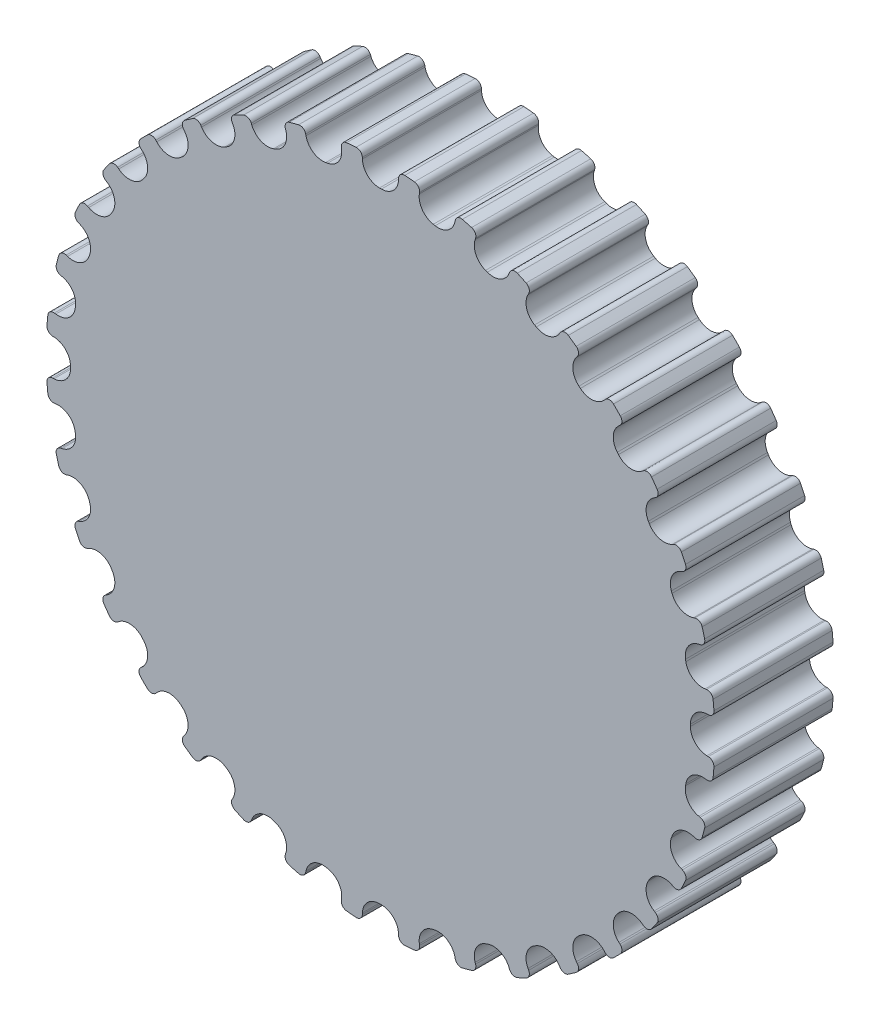
SolidWorks part; units mm, degrees
material "ABS"
ref_plane "前视基准面" through (0, 0, 0) normal (0, 0, 1) x (1, 0, 0)
ref_plane "上视基准面" through (0, 0, 0) normal (0, 1, 0) x (1, 0, 0)
ref_plane "右视基准面" through (0, 0, 0) normal (1, 0, 0) x (0, 0, -1)
sketch "草图1" plane through (0, 0, 0) normal (0, 0, 1) x (1, 0, 0)
  line L0 (0, 0) -> (0, 28.0759) construction
  line L1 (-2.5, 27.9644) -> (2.5, 27.9644) construction
  line L2 (-0.081, 26.0239) -> (0.081, 26.0239)
  line L3 (1.5181, 27.4117) -> (1.5223, 27.5316)
  line L4 (-1.5181, 27.4117) -> (-1.5223, 27.5316)
  line L5 (3.2649, 27.2589) -> (3.2816, 27.3777)
  line L6 (4.4392, 25.6426) -> (4.5988, 25.6145)
  line L7 (6.2551, 26.7316) -> (6.28, 26.849)
  line L8 (7.9488, 26.2778) -> (7.9859, 26.3919)
  line L9 (8.8246, 24.4822) -> (8.9768, 24.4268)
  line L10 (10.8019, 25.2393) -> (10.8469, 25.3506)
  line L11 (12.3911, 24.4983) -> (12.4474, 24.6042)
  line L12 (12.9418, 22.5778) -> (13.0821, 22.4968)
  line L13 (15.0206, 22.9802) -> (15.0842, 23.0819)
  line L14 (16.457, 21.9744) -> (16.5308, 22.069)
  line L15 (16.6658, 19.9875) -> (16.7899, 19.8834)
  line L16 (18.7829, 20.0228) -> (18.8631, 20.1119)
  line L17 (20.0228, 18.7829) -> (20.1119, 18.8631)
  line L18 (19.8834, 16.7899) -> (19.9875, 16.6658)
  line L19 (21.9744, 16.457) -> (22.069, 16.5308)
  line L20 (22.9802, 15.0206) -> (23.0819, 15.0842)
  line L21 (22.4968, 13.0821) -> (22.5778, 12.9418)
  line L22 (24.4983, 12.3911) -> (24.6042, 12.4474)
  line L23 (25.2393, 10.8019) -> (25.3506, 10.8469)
  line L24 (24.4268, 8.9768) -> (24.4822, 8.8246)
  line L25 (26.2778, 7.9488) -> (26.3919, 7.9859)
  line L26 (26.7316, 6.2551) -> (26.849, 6.28)
  line L27 (25.6145, 4.5988) -> (25.6426, 4.4392)
  line L28 (27.2589, 3.2649) -> (27.3777, 3.2816)
  line L29 (27.4117, 1.5181) -> (27.5316, 1.5223)
  line L30 (26.0239, 0.081) -> (26.0239, -0.081)
  line L31 (27.4117, -1.5181) -> (27.5316, -1.5223)
  line L32 (27.2589, -3.2649) -> (27.3777, -3.2816)
  line L33 (25.6426, -4.4392) -> (25.6145, -4.5988)
  line L34 (26.7316, -6.2551) -> (26.849, -6.28)
  line L35 (26.2778, -7.9488) -> (26.3919, -7.9859)
  line L36 (24.4822, -8.8246) -> (24.4268, -8.9768)
  line L37 (25.2393, -10.8019) -> (25.3506, -10.8469)
  line L38 (24.4983, -12.3911) -> (24.6042, -12.4474)
  line L39 (22.5778, -12.9418) -> (22.4968, -13.0821)
  line L40 (22.9802, -15.0206) -> (23.0819, -15.0842)
  line L41 (21.9744, -16.457) -> (22.069, -16.5308)
  line L42 (19.9875, -16.6658) -> (19.8834, -16.7899)
  line L43 (20.0228, -18.7829) -> (20.1119, -18.8631)
  line L44 (18.7829, -20.0228) -> (18.8631, -20.1119)
  line L45 (16.7899, -19.8834) -> (16.6658, -19.9875)
  line L46 (16.457, -21.9744) -> (16.5308, -22.069)
  line L47 (15.0206, -22.9802) -> (15.0842, -23.0819)
  line L48 (13.0821, -22.4968) -> (12.9418, -22.5778)
  line L49 (12.3911, -24.4983) -> (12.4474, -24.6042)
  line L50 (10.8019, -25.2393) -> (10.8469, -25.3506)
  line L51 (8.9768, -24.4268) -> (8.8246, -24.4822)
  line L52 (7.9488, -26.2778) -> (7.9859, -26.3919)
  line L53 (6.2551, -26.7316) -> (6.28, -26.849)
  line L54 (4.5988, -25.6145) -> (4.4392, -25.6426)
  line L55 (3.2649, -27.2589) -> (3.2816, -27.3777)
  line L56 (1.5181, -27.4117) -> (1.5223, -27.5316)
  line L57 (0.081, -26.0239) -> (-0.081, -26.0239)
  line L58 (-1.5181, -27.4117) -> (-1.5223, -27.5316)
  line L59 (-3.2649, -27.2589) -> (-3.2816, -27.3777)
  line L60 (-4.4392, -25.6426) -> (-4.5988, -25.6145)
  line L61 (-6.2551, -26.7316) -> (-6.28, -26.849)
  line L62 (-7.9488, -26.2778) -> (-7.9859, -26.3919)
  line L63 (-8.8246, -24.4822) -> (-8.9768, -24.4268)
  line L64 (-10.8019, -25.2393) -> (-10.8469, -25.3506)
  line L65 (-12.3911, -24.4983) -> (-12.4474, -24.6042)
  line L66 (-12.9418, -22.5778) -> (-13.0821, -22.4968)
  line L67 (-15.0206, -22.9802) -> (-15.0842, -23.0819)
  line L68 (-16.457, -21.9744) -> (-16.5308, -22.069)
  line L69 (-16.6658, -19.9875) -> (-16.7899, -19.8834)
  line L70 (-18.7829, -20.0228) -> (-18.8631, -20.1119)
  line L71 (-20.0228, -18.7829) -> (-20.1119, -18.8631)
  line L72 (-19.8834, -16.7899) -> (-19.9875, -16.6658)
  line L73 (-21.9744, -16.457) -> (-22.069, -16.5308)
  line L74 (-22.9802, -15.0206) -> (-23.0819, -15.0842)
  line L75 (-22.4968, -13.0821) -> (-22.5778, -12.9418)
  line L76 (-24.4983, -12.3911) -> (-24.6042, -12.4474)
  line L77 (-25.2393, -10.8019) -> (-25.3506, -10.8469)
  line L78 (-24.4268, -8.9768) -> (-24.4822, -8.8246)
  line L79 (-26.2778, -7.9488) -> (-26.3919, -7.9859)
  line L80 (-26.7316, -6.2551) -> (-26.849, -6.28)
  line L81 (-25.6145, -4.5988) -> (-25.6426, -4.4392)
  line L82 (-27.2589, -3.2649) -> (-27.3777, -3.2816)
  line L83 (-27.4117, -1.5181) -> (-27.5316, -1.5223)
  line L84 (-26.0239, -0.081) -> (-26.0239, 0.081)
  line L85 (-27.4117, 1.5181) -> (-27.5316, 1.5223)
  line L86 (-27.2589, 3.2649) -> (-27.3777, 3.2816)
  line L87 (-25.6426, 4.4392) -> (-25.6145, 4.5988)
  line L88 (-26.7316, 6.2551) -> (-26.849, 6.28)
  line L89 (-26.2778, 7.9488) -> (-26.3919, 7.9859)
  line L90 (-24.4822, 8.8246) -> (-24.4268, 8.9768)
  line L91 (-25.2393, 10.8019) -> (-25.3506, 10.8469)
  line L92 (-24.4983, 12.3911) -> (-24.6042, 12.4474)
  line L93 (-22.5778, 12.9418) -> (-22.4968, 13.0821)
  line L94 (-22.9802, 15.0206) -> (-23.0819, 15.0842)
  line L95 (-21.9744, 16.457) -> (-22.069, 16.5308)
  line L96 (-19.9875, 16.6658) -> (-19.8834, 16.7899)
  line L97 (-20.0228, 18.7829) -> (-20.1119, 18.8631)
  line L98 (-18.7829, 20.0228) -> (-18.8631, 20.1119)
  line L99 (-16.7899, 19.8834) -> (-16.6658, 19.9875)
  line L100 (-16.457, 21.9744) -> (-16.5308, 22.069)
  line L101 (-15.0206, 22.9802) -> (-15.0842, 23.0819)
  line L102 (-13.0821, 22.4968) -> (-12.9418, 22.5778)
  line L103 (-12.3911, 24.4983) -> (-12.4474, 24.6042)
  line L104 (-10.8019, 25.2393) -> (-10.8469, 25.3506)
  line L105 (-8.9768, 24.4268) -> (-8.8246, 24.4822)
  line L106 (-7.9488, 26.2778) -> (-7.9859, 26.3919)
  line L107 (-6.2551, 26.7316) -> (-6.28, 26.849)
  line L108 (-4.5988, 25.6145) -> (-4.4392, 25.6426)
  line L109 (-3.2649, 27.2589) -> (-3.2816, 27.3777)
  circle A0 centre (0, 0) radius 28.0759 construction
  arc A1 (0.081, 26.0239) -> (1.5181, 27.4117) centre (0.081, 27.4619) ccw
  arc A2 (1.5223, 27.5316) -> (2.0456, 28.0013) centre (2.01, 27.5146) cw
  arc A3 (2.0456, 28.0013) -> (2.5, 27.9644) centre (0, 0) cw
  arc A4 (-2.0456, 28.0013) -> (-2.5, 27.9644) centre (0, 0) ccw
  arc A5 (-1.5223, 27.5316) -> (-2.0456, 28.0013) centre (-2.01, 27.5146) ccw
  arc A6 (-0.081, 26.0239) -> (-1.5181, 27.4117) centre (-0.081, 27.4619) cw
  arc A7 (2.8479, 27.9311) -> (2.3939, 27.9736) centre (0, 0) ccw
  arc A8 (3.2816, 27.3777) -> (2.8479, 27.9311) centre (2.7984, 27.4456) ccw
  arc A9 (4.4392, 25.6426) -> (3.2649, 27.2589) centre (4.6889, 27.0587) cw
  arc A10 (4.5988, 25.6145) -> (6.2551, 26.7316) centre (4.8485, 27.0306) ccw
  arc A11 (6.28, 26.849) -> (6.8769, 27.2207) centre (6.7573, 26.7475) cw
  arc A12 (6.8769, 27.2207) -> (7.318, 27.1054) centre (0, 0) cw
  arc A13 (7.6548, 27.0122) -> (7.2151, 27.133) centre (0, 0) ccw
  arc A14 (7.9859, 26.3919) -> (7.6548, 27.0122) centre (7.5217, 26.5427) ccw
  arc A15 (8.8246, 24.4822) -> (7.9488, 26.2778) centre (9.3164, 25.8334) cw
  arc A16 (8.9768, 24.4268) -> (10.8019, 25.2393) centre (9.4686, 25.778) ccw
  arc A17 (10.8469, 25.3506) -> (11.4992, 25.613) centre (11.2993, 25.1678) cw
  arc A18 (11.4992, 25.613) -> (11.9136, 25.4229) centre (0, 0) cw
  arc A19 (12.2291, 25.2726) -> (11.8171, 25.4678) centre (0, 0) ccw
  arc A20 (12.4474, 24.6042) -> (12.2291, 25.2726) centre (12.0166, 24.8333) ccw
  arc A21 (12.9418, 22.5778) -> (12.3911, 24.4983) centre (13.6608, 23.8232) cw
  arc A22 (13.0821, 22.4968) -> (15.0206, 22.9802) centre (13.8011, 23.7422) ccw
  arc A23 (15.0842, 23.0819) -> (15.7722, 23.227) centre (15.498, 22.8233) cw
  arc A24 (15.7722, 23.227) -> (16.1472, 22.9678) centre (0, 0) cw
  arc A25 (16.4319, 22.7651) -> (16.06, 23.0289) centre (0, 0) ccw
  arc A26 (16.5308, 22.069) -> (16.4319, 22.7651) centre (16.1463, 22.3694) ccw
  arc A27 (16.6658, 19.9875) -> (16.457, 21.9744) centre (17.5901, 21.0891) cw
  arc A28 (16.7899, 19.8834) -> (18.7829, 20.0228) centre (17.7142, 20.985) ccw
  arc A29 (18.8631, 20.1119) -> (19.5659, 20.1354) centre (19.2258, 19.7854) cw
  arc A30 (19.5659, 20.1354) -> (19.8903, 19.815) centre (0, 0) cw
  arc A31 (20.1354, 19.5659) -> (19.815, 19.8903) centre (0, 0) ccw
  arc A32 (20.1119, 18.8631) -> (20.1354, 19.5659) centre (19.7854, 19.2258) ccw
  arc A33 (19.8834, 16.7899) -> (20.0228, 18.7829) centre (20.985, 17.7142) cw
  arc A34 (19.9875, 16.6658) -> (21.9744, 16.457) centre (21.0891, 17.5901) ccw
  arc A35 (22.069, 16.5308) -> (22.7651, 16.4319) centre (22.3694, 16.1463) cw
  arc A36 (22.7651, 16.4319) -> (23.0289, 16.06) centre (0, 0) cw
  arc A37 (23.227, 15.7722) -> (22.9678, 16.1472) centre (0, 0) ccw
  arc A38 (23.0819, 15.0842) -> (23.227, 15.7722) centre (22.8233, 15.498) ccw
  arc A39 (22.4968, 13.0821) -> (22.9802, 15.0206) centre (23.7422, 13.8011) cw
  arc A40 (22.5778, 12.9418) -> (24.4983, 12.3911) centre (23.8232, 13.6608) ccw
  arc A41 (24.6042, 12.4474) -> (25.2726, 12.2291) centre (24.8333, 12.0166) cw
  arc A42 (25.2726, 12.2291) -> (25.4678, 11.8171) centre (0, 0) cw
  arc A43 (25.613, 11.4992) -> (25.4229, 11.9136) centre (0, 0) ccw
  arc A44 (25.3506, 10.8469) -> (25.613, 11.4992) centre (25.1678, 11.2993) ccw
  arc A45 (24.4268, 8.9768) -> (25.2393, 10.8019) centre (25.778, 9.4686) cw
  arc A46 (24.4822, 8.8246) -> (26.2778, 7.9488) centre (25.8334, 9.3164) ccw
  arc A47 (26.3919, 7.9859) -> (27.0122, 7.6548) centre (26.5427, 7.5217) cw
  arc A48 (27.0122, 7.6548) -> (27.133, 7.2151) centre (0, 0) cw
  arc A49 (27.2207, 6.8769) -> (27.1054, 7.318) centre (0, 0) ccw
  arc A50 (26.849, 6.28) -> (27.2207, 6.8769) centre (26.7475, 6.7573) ccw
  arc A51 (25.6145, 4.5988) -> (26.7316, 6.2551) centre (27.0306, 4.8485) cw
  arc A52 (25.6426, 4.4392) -> (27.2589, 3.2649) centre (27.0587, 4.6889) ccw
  arc A53 (27.3777, 3.2816) -> (27.9311, 2.8479) centre (27.4456, 2.7984) cw
  arc A54 (27.9311, 2.8479) -> (27.9736, 2.3939) centre (0, 0) cw
  arc A55 (28.0013, 2.0456) -> (27.9644, 2.5) centre (0, 0) ccw
  arc A56 (27.5316, 1.5223) -> (28.0013, 2.0456) centre (27.5146, 2.01) ccw
  arc A57 (26.0239, 0.081) -> (27.4117, 1.5181) centre (27.4619, 0.081) cw
  arc A58 (26.0239, -0.081) -> (27.4117, -1.5181) centre (27.4619, -0.081) ccw
  arc A59 (27.5316, -1.5223) -> (28.0013, -2.0456) centre (27.5146, -2.01) cw
  arc A60 (28.0013, -2.0456) -> (27.9644, -2.5) centre (0, 0) cw
  arc A61 (27.9311, -2.8479) -> (27.9736, -2.3939) centre (0, 0) ccw
  arc A62 (27.3777, -3.2816) -> (27.9311, -2.8479) centre (27.4456, -2.7984) ccw
  arc A63 (25.6426, -4.4392) -> (27.2589, -3.2649) centre (27.0587, -4.6889) cw
  arc A64 (25.6145, -4.5988) -> (26.7316, -6.2551) centre (27.0306, -4.8485) ccw
  arc A65 (26.849, -6.28) -> (27.2207, -6.8769) centre (26.7475, -6.7573) cw
  arc A66 (27.2207, -6.8769) -> (27.1054, -7.318) centre (0, 0) cw
  arc A67 (27.0122, -7.6548) -> (27.133, -7.2151) centre (0, 0) ccw
  arc A68 (26.3919, -7.9859) -> (27.0122, -7.6548) centre (26.5427, -7.5217) ccw
  arc A69 (24.4822, -8.8246) -> (26.2778, -7.9488) centre (25.8334, -9.3164) cw
  arc A70 (24.4268, -8.9768) -> (25.2393, -10.8019) centre (25.778, -9.4686) ccw
  arc A71 (25.3506, -10.8469) -> (25.613, -11.4992) centre (25.1678, -11.2993) cw
  arc A72 (25.613, -11.4992) -> (25.4229, -11.9136) centre (0, 0) cw
  arc A73 (25.2726, -12.2291) -> (25.4678, -11.8171) centre (0, 0) ccw
  arc A74 (24.6042, -12.4474) -> (25.2726, -12.2291) centre (24.8333, -12.0166) ccw
  arc A75 (22.5778, -12.9418) -> (24.4983, -12.3911) centre (23.8232, -13.6608) cw
  arc A76 (22.4968, -13.0821) -> (22.9802, -15.0206) centre (23.7422, -13.8011) ccw
  arc A77 (23.0819, -15.0842) -> (23.227, -15.7722) centre (22.8233, -15.498) cw
  arc A78 (23.227, -15.7722) -> (22.9678, -16.1472) centre (0, 0) cw
  arc A79 (22.7651, -16.4319) -> (23.0289, -16.06) centre (0, 0) ccw
  arc A80 (22.069, -16.5308) -> (22.7651, -16.4319) centre (22.3694, -16.1463) ccw
  arc A81 (19.9875, -16.6658) -> (21.9744, -16.457) centre (21.0891, -17.5901) cw
  arc A82 (19.8834, -16.7899) -> (20.0228, -18.7829) centre (20.985, -17.7142) ccw
  arc A83 (20.1119, -18.8631) -> (20.1354, -19.5659) centre (19.7854, -19.2258) cw
  arc A84 (20.1354, -19.5659) -> (19.815, -19.8903) centre (0, 0) cw
  arc A85 (19.5659, -20.1354) -> (19.8903, -19.815) centre (0, 0) ccw
  arc A86 (18.8631, -20.1119) -> (19.5659, -20.1354) centre (19.2258, -19.7854) ccw
  arc A87 (16.7899, -19.8834) -> (18.7829, -20.0228) centre (17.7142, -20.985) cw
  arc A88 (16.6658, -19.9875) -> (16.457, -21.9744) centre (17.5901, -21.0891) ccw
  arc A89 (16.5308, -22.069) -> (16.4319, -22.7651) centre (16.1463, -22.3694) cw
  arc A90 (16.4319, -22.7651) -> (16.06, -23.0289) centre (0, 0) cw
  arc A91 (15.7722, -23.227) -> (16.1472, -22.9678) centre (0, 0) ccw
  arc A92 (15.0842, -23.0819) -> (15.7722, -23.227) centre (15.498, -22.8233) ccw
  arc A93 (13.0821, -22.4968) -> (15.0206, -22.9802) centre (13.8011, -23.7422) cw
  arc A94 (12.9418, -22.5778) -> (12.3911, -24.4983) centre (13.6608, -23.8232) ccw
  arc A95 (12.4474, -24.6042) -> (12.2291, -25.2726) centre (12.0166, -24.8333) cw
  arc A96 (12.2291, -25.2726) -> (11.8171, -25.4678) centre (0, 0) cw
  arc A97 (11.4992, -25.613) -> (11.9136, -25.4229) centre (0, 0) ccw
  arc A98 (10.8469, -25.3506) -> (11.4992, -25.613) centre (11.2993, -25.1678) ccw
  arc A99 (8.9768, -24.4268) -> (10.8019, -25.2393) centre (9.4686, -25.778) cw
  arc A100 (8.8246, -24.4822) -> (7.9488, -26.2778) centre (9.3164, -25.8334) ccw
  arc A101 (7.9859, -26.3919) -> (7.6548, -27.0122) centre (7.5217, -26.5427) cw
  arc A102 (7.6548, -27.0122) -> (7.2151, -27.133) centre (0, 0) cw
  arc A103 (6.8769, -27.2207) -> (7.318, -27.1054) centre (0, 0) ccw
  arc A104 (6.28, -26.849) -> (6.8769, -27.2207) centre (6.7573, -26.7475) ccw
  arc A105 (4.5988, -25.6145) -> (6.2551, -26.7316) centre (4.8485, -27.0306) cw
  arc A106 (4.4392, -25.6426) -> (3.2649, -27.2589) centre (4.6889, -27.0587) ccw
  arc A107 (3.2816, -27.3777) -> (2.8479, -27.9311) centre (2.7984, -27.4456) cw
  arc A108 (2.8479, -27.9311) -> (2.3939, -27.9736) centre (0, 0) cw
  arc A109 (2.0456, -28.0013) -> (2.5, -27.9644) centre (0, 0) ccw
  arc A110 (1.5223, -27.5316) -> (2.0456, -28.0013) centre (2.01, -27.5146) ccw
  arc A111 (0.081, -26.0239) -> (1.5181, -27.4117) centre (0.081, -27.4619) cw
  arc A112 (-0.081, -26.0239) -> (-1.5181, -27.4117) centre (-0.081, -27.4619) ccw
  arc A113 (-1.5223, -27.5316) -> (-2.0456, -28.0013) centre (-2.01, -27.5146) cw
  arc A114 (-2.0456, -28.0013) -> (-2.5, -27.9644) centre (0, 0) cw
  arc A115 (-2.8479, -27.9311) -> (-2.3939, -27.9736) centre (0, 0) ccw
  arc A116 (-3.2816, -27.3777) -> (-2.8479, -27.9311) centre (-2.7984, -27.4456) ccw
  arc A117 (-4.4392, -25.6426) -> (-3.2649, -27.2589) centre (-4.6889, -27.0587) cw
  arc A118 (-4.5988, -25.6145) -> (-6.2551, -26.7316) centre (-4.8485, -27.0306) ccw
  arc A119 (-6.28, -26.849) -> (-6.8769, -27.2207) centre (-6.7573, -26.7475) cw
  arc A120 (-6.8769, -27.2207) -> (-7.318, -27.1054) centre (0, 0) cw
  arc A121 (-7.6548, -27.0122) -> (-7.2151, -27.133) centre (0, 0) ccw
  arc A122 (-7.9859, -26.3919) -> (-7.6548, -27.0122) centre (-7.5217, -26.5427) ccw
  arc A123 (-8.8246, -24.4822) -> (-7.9488, -26.2778) centre (-9.3164, -25.8334) cw
  arc A124 (-8.9768, -24.4268) -> (-10.8019, -25.2393) centre (-9.4686, -25.778) ccw
  arc A125 (-10.8469, -25.3506) -> (-11.4992, -25.613) centre (-11.2993, -25.1678) cw
  arc A126 (-11.4992, -25.613) -> (-11.9136, -25.4229) centre (0, 0) cw
  arc A127 (-12.2291, -25.2726) -> (-11.8171, -25.4678) centre (0, 0) ccw
  arc A128 (-12.4474, -24.6042) -> (-12.2291, -25.2726) centre (-12.0166, -24.8333) ccw
  arc A129 (-12.9418, -22.5778) -> (-12.3911, -24.4983) centre (-13.6608, -23.8232) cw
  arc A130 (-13.0821, -22.4968) -> (-15.0206, -22.9802) centre (-13.8011, -23.7422) ccw
  arc A131 (-15.0842, -23.0819) -> (-15.7722, -23.227) centre (-15.498, -22.8233) cw
  arc A132 (-15.7722, -23.227) -> (-16.1472, -22.9678) centre (0, 0) cw
  arc A133 (-16.4319, -22.7651) -> (-16.06, -23.0289) centre (0, 0) ccw
  arc A134 (-16.5308, -22.069) -> (-16.4319, -22.7651) centre (-16.1463, -22.3694) ccw
  arc A135 (-16.6658, -19.9875) -> (-16.457, -21.9744) centre (-17.5901, -21.0891) cw
  arc A136 (-16.7899, -19.8834) -> (-18.7829, -20.0228) centre (-17.7142, -20.985) ccw
  arc A137 (-18.8631, -20.1119) -> (-19.5659, -20.1354) centre (-19.2258, -19.7854) cw
  arc A138 (-19.5659, -20.1354) -> (-19.8903, -19.815) centre (0, 0) cw
  arc A139 (-20.1354, -19.5659) -> (-19.815, -19.8903) centre (0, 0) ccw
  arc A140 (-20.1119, -18.8631) -> (-20.1354, -19.5659) centre (-19.7854, -19.2258) ccw
  arc A141 (-19.8834, -16.7899) -> (-20.0228, -18.7829) centre (-20.985, -17.7142) cw
  arc A142 (-19.9875, -16.6658) -> (-21.9744, -16.457) centre (-21.0891, -17.5901) ccw
  arc A143 (-22.069, -16.5308) -> (-22.7651, -16.4319) centre (-22.3694, -16.1463) cw
  arc A144 (-22.7651, -16.4319) -> (-23.0289, -16.06) centre (0, 0) cw
  arc A145 (-23.227, -15.7722) -> (-22.9678, -16.1472) centre (0, 0) ccw
  arc A146 (-23.0819, -15.0842) -> (-23.227, -15.7722) centre (-22.8233, -15.498) ccw
  arc A147 (-22.4968, -13.0821) -> (-22.9802, -15.0206) centre (-23.7422, -13.8011) cw
  arc A148 (-22.5778, -12.9418) -> (-24.4983, -12.3911) centre (-23.8232, -13.6608) ccw
  arc A149 (-24.6042, -12.4474) -> (-25.2726, -12.2291) centre (-24.8333, -12.0166) cw
  arc A150 (-25.2726, -12.2291) -> (-25.4678, -11.8171) centre (0, 0) cw
  arc A151 (-25.613, -11.4992) -> (-25.4229, -11.9136) centre (0, 0) ccw
  arc A152 (-25.3506, -10.8469) -> (-25.613, -11.4992) centre (-25.1678, -11.2993) ccw
  arc A153 (-24.4268, -8.9768) -> (-25.2393, -10.8019) centre (-25.778, -9.4686) cw
  arc A154 (-24.4822, -8.8246) -> (-26.2778, -7.9488) centre (-25.8334, -9.3164) ccw
  arc A155 (-26.3919, -7.9859) -> (-27.0122, -7.6548) centre (-26.5427, -7.5217) cw
  arc A156 (-27.0122, -7.6548) -> (-27.133, -7.2151) centre (0, 0) cw
  arc A157 (-27.2207, -6.8769) -> (-27.1054, -7.318) centre (0, 0) ccw
  arc A158 (-26.849, -6.28) -> (-27.2207, -6.8769) centre (-26.7475, -6.7573) ccw
  arc A159 (-25.6145, -4.5988) -> (-26.7316, -6.2551) centre (-27.0306, -4.8485) cw
  arc A160 (-25.6426, -4.4392) -> (-27.2589, -3.2649) centre (-27.0587, -4.6889) ccw
  arc A161 (-27.3777, -3.2816) -> (-27.9311, -2.8479) centre (-27.4456, -2.7984) cw
  arc A162 (-27.9311, -2.8479) -> (-27.9736, -2.3939) centre (0, 0) cw
  arc A163 (-28.0013, -2.0456) -> (-27.9644, -2.5) centre (0, 0) ccw
  arc A164 (-27.5316, -1.5223) -> (-28.0013, -2.0456) centre (-27.5146, -2.01) ccw
  arc A165 (-26.0239, -0.081) -> (-27.4117, -1.5181) centre (-27.4619, -0.081) cw
  arc A166 (-26.0239, 0.081) -> (-27.4117, 1.5181) centre (-27.4619, 0.081) ccw
  arc A167 (-27.5316, 1.5223) -> (-28.0013, 2.0456) centre (-27.5146, 2.01) cw
  arc A168 (-28.0013, 2.0456) -> (-27.9644, 2.5) centre (0, 0) cw
  arc A169 (-27.9311, 2.8479) -> (-27.9736, 2.3939) centre (0, 0) ccw
  arc A170 (-27.3777, 3.2816) -> (-27.9311, 2.8479) centre (-27.4456, 2.7984) ccw
  arc A171 (-25.6426, 4.4392) -> (-27.2589, 3.2649) centre (-27.0587, 4.6889) cw
  arc A172 (-25.6145, 4.5988) -> (-26.7316, 6.2551) centre (-27.0306, 4.8485) ccw
  arc A173 (-26.849, 6.28) -> (-27.2207, 6.8769) centre (-26.7475, 6.7573) cw
  arc A174 (-27.2207, 6.8769) -> (-27.1054, 7.318) centre (0, 0) cw
  arc A175 (-27.0122, 7.6548) -> (-27.133, 7.2151) centre (0, 0) ccw
  arc A176 (-26.3919, 7.9859) -> (-27.0122, 7.6548) centre (-26.5427, 7.5217) ccw
  arc A177 (-24.4822, 8.8246) -> (-26.2778, 7.9488) centre (-25.8334, 9.3164) cw
  arc A178 (-24.4268, 8.9768) -> (-25.2393, 10.8019) centre (-25.778, 9.4686) ccw
  arc A179 (-25.3506, 10.8469) -> (-25.613, 11.4992) centre (-25.1678, 11.2993) cw
  arc A180 (-25.613, 11.4992) -> (-25.4229, 11.9136) centre (0, 0) cw
  arc A181 (-25.2726, 12.2291) -> (-25.4678, 11.8171) centre (0, 0) ccw
  arc A182 (-24.6042, 12.4474) -> (-25.2726, 12.2291) centre (-24.8333, 12.0166) ccw
  arc A183 (-22.5778, 12.9418) -> (-24.4983, 12.3911) centre (-23.8232, 13.6608) cw
  arc A184 (-22.4968, 13.0821) -> (-22.9802, 15.0206) centre (-23.7422, 13.8011) ccw
  arc A185 (-23.0819, 15.0842) -> (-23.227, 15.7722) centre (-22.8233, 15.498) cw
  arc A186 (-23.227, 15.7722) -> (-22.9678, 16.1472) centre (0, 0) cw
  arc A187 (-22.7651, 16.4319) -> (-23.0289, 16.06) centre (0, 0) ccw
  arc A188 (-22.069, 16.5308) -> (-22.7651, 16.4319) centre (-22.3694, 16.1463) ccw
  arc A189 (-19.9875, 16.6658) -> (-21.9744, 16.457) centre (-21.0891, 17.5901) cw
  arc A190 (-19.8834, 16.7899) -> (-20.0228, 18.7829) centre (-20.985, 17.7142) ccw
  arc A191 (-20.1119, 18.8631) -> (-20.1354, 19.5659) centre (-19.7854, 19.2258) cw
  arc A192 (-20.1354, 19.5659) -> (-19.815, 19.8903) centre (0, 0) cw
  arc A193 (-19.5659, 20.1354) -> (-19.8903, 19.815) centre (0, 0) ccw
  arc A194 (-18.8631, 20.1119) -> (-19.5659, 20.1354) centre (-19.2258, 19.7854) ccw
  arc A195 (-16.7899, 19.8834) -> (-18.7829, 20.0228) centre (-17.7142, 20.985) cw
  arc A196 (-16.6658, 19.9875) -> (-16.457, 21.9744) centre (-17.5901, 21.0891) ccw
  arc A197 (-16.5308, 22.069) -> (-16.4319, 22.7651) centre (-16.1463, 22.3694) cw
  arc A198 (-16.4319, 22.7651) -> (-16.06, 23.0289) centre (0, 0) cw
  arc A199 (-15.7722, 23.227) -> (-16.1472, 22.9678) centre (0, 0) ccw
  arc A200 (-15.0842, 23.0819) -> (-15.7722, 23.227) centre (-15.498, 22.8233) ccw
  arc A201 (-13.0821, 22.4968) -> (-15.0206, 22.9802) centre (-13.8011, 23.7422) cw
  arc A202 (-12.9418, 22.5778) -> (-12.3911, 24.4983) centre (-13.6608, 23.8232) ccw
  arc A203 (-12.4474, 24.6042) -> (-12.2291, 25.2726) centre (-12.0166, 24.8333) cw
  arc A204 (-12.2291, 25.2726) -> (-11.8171, 25.4678) centre (0, 0) cw
  arc A205 (-11.4992, 25.613) -> (-11.9136, 25.4229) centre (0, 0) ccw
  arc A206 (-10.8469, 25.3506) -> (-11.4992, 25.613) centre (-11.2993, 25.1678) ccw
  arc A207 (-8.9768, 24.4268) -> (-10.8019, 25.2393) centre (-9.4686, 25.778) cw
  arc A208 (-8.8246, 24.4822) -> (-7.9488, 26.2778) centre (-9.3164, 25.8334) ccw
  arc A209 (-7.9859, 26.3919) -> (-7.6548, 27.0122) centre (-7.5217, 26.5427) cw
  arc A210 (-7.6548, 27.0122) -> (-7.2151, 27.133) centre (0, 0) cw
  arc A211 (-6.8769, 27.2207) -> (-7.318, 27.1054) centre (0, 0) ccw
  arc A212 (-6.28, 26.849) -> (-6.8769, 27.2207) centre (-6.7573, 26.7475) ccw
  arc A213 (-4.5988, 25.6145) -> (-6.2551, 26.7316) centre (-4.8485, 27.0306) cw
  arc A214 (-4.4392, 25.6426) -> (-3.2649, 27.2589) centre (-4.6889, 27.0587) ccw
  arc A215 (-3.2816, 27.3777) -> (-2.8479, 27.9311) centre (-2.7984, 27.4456) cw
  arc A216 (-2.8479, 27.9311) -> (-2.3939, 27.9736) centre (0, 0) cw
  point P20 (0, 26.0239)
  point P512 (0, 0)
  dimension "外径" = 56.1518
  dimension "R1" = 1.438
  dimension "R2" = 0.488
  dimension "节距" = 5
  dimension "Hg" = 2.052
  dimension "X" = 0.081
  dimension "φ" = 2
  dimension "齿数" = 36
extrude "带轮齿形" add sketch "草图1" along normal mid plane 10 contours A120 A119 L61 A118 L60 A117 L59 A116 A115 A114 A113 L58 A112 L57 A111 L56 A110 A109 A108 A107 L55 A106 L54 A105 L53 A104 A103 A102 A101 L52 A100 L51 A99 L50 A98 A97 A96 A95 L49 A94 L48 A93 L47 A92 A91 A90 region at (0, 0, 0)
sketch "草图2" plane through (0, 0, -5) normal (0, 0, -1) x (-1, 0, 0)
  circle A0 centre (0, 0) radius 29.5759
  dimension "档边直径" = 59.1518
extrude "档边" [suppressed] add sketch "草图2" along normal blind 2
chamfer "倒角1" [suppressed] distance 1.5 angle 45
mirror "需要档边解压缩选项" [suppressed] about plane through (0, 0, 0) normal (0, 0, 1)
sketch "节径" plane through (0, 0, 0) normal (0, 0, 1) x (1, 0, 0)
  circle A0 centre (0, 0) radius 28.6479
  dimension "节径" = 57.2958
